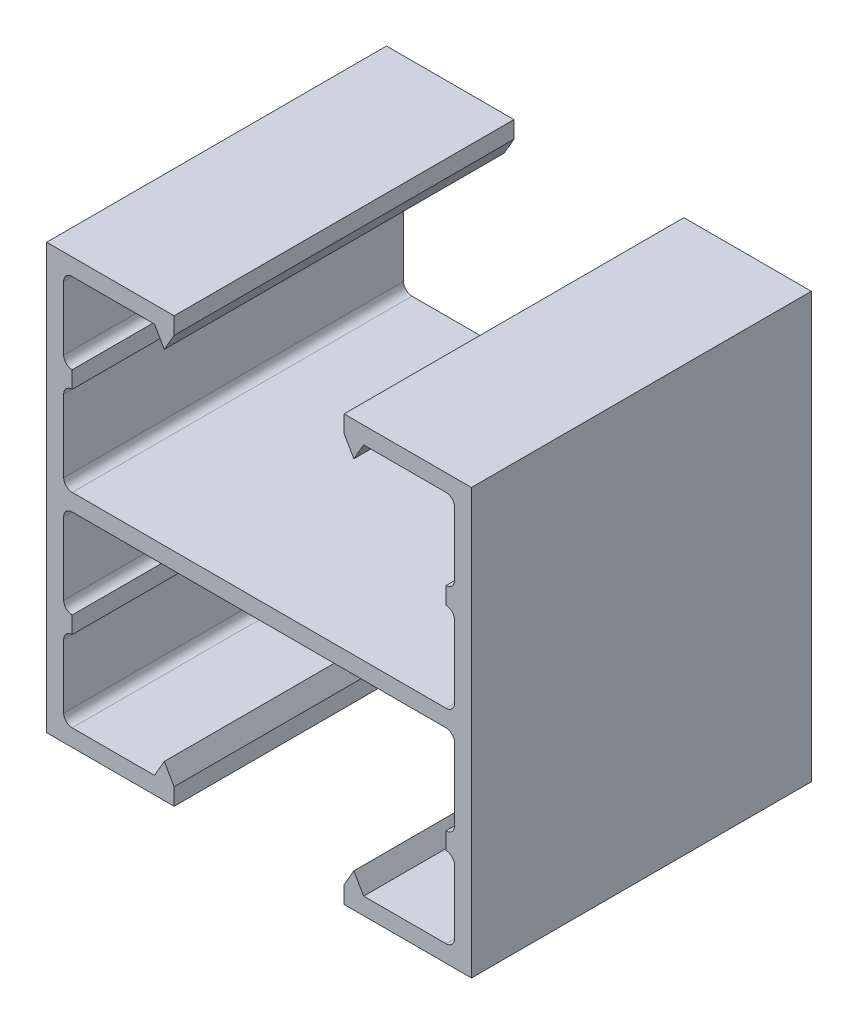
SolidWorks part; units mm, degrees
ref_plane "Plane1" through (0, 0, 0) normal (0, 0, 1) x (1, 0, 0)
ref_plane "Plane2" through (0, 0, 0) normal (0, 1, 0) x (1, 0, 0)
ref_plane "Plane3" through (0, 0, 0) normal (1, 0, 0) x (0, 0, -1)
sketch "Sketch1" plane through (0, 0, 0) normal (0, 0, 1) x (1, 0, 0)
  line L0 (-6.35, 15.875) -> (-15.875, 15.875)
  line L1 (-15.875, 15.875) -> (-15.875, -15.875)
  line L2 (-7.8165, -14.605) -> (-13.97, -14.605)
  line L3 (15.875, -15.875) -> (15.875, 15.875)
  line L4 (15.875, 15.875) -> (6.35, 15.875)
  line L5 (13.97, 14.605) -> (7.8165, 14.605)
  line L6 (14.605, 1.27) -> (14.605, 7.3025)
  line L7 (-13.97, 0.635) -> (13.97, 0.635)
  line L8 (-14.605, 13.97) -> (-14.605, 8.5725)
  line L9 (-7.8165, 14.605) -> (-13.97, 14.605)
  line L10 (7.8165, 14.605) -> (7.0832, 13.335)
  line L11 (7.0832, 13.335) -> (6.35, 14.605)
  line L12 (6.35, 14.605) -> (6.35, 15.875)
  line L13 (-7.8165, 14.605) -> (-7.0832, 13.335)
  line L14 (-7.0832, 13.335) -> (-6.35, 14.605)
  line L15 (-6.35, 14.605) -> (-6.35, 15.875)
  line L16 (22.86, 0) -> (-25.4, 0) construction
  line L17 (7.0832, -13.335) -> (6.35, -14.605)
  line L18 (7.8165, -14.605) -> (7.0832, -13.335)
  line L19 (13.97, -14.605) -> (7.8165, -14.605)
  line L20 (15.875, -15.875) -> (6.35, -15.875)
  line L21 (6.35, -14.605) -> (6.35, -15.875)
  line L22 (-6.35, -15.875) -> (-15.875, -15.875)
  line L23 (-6.35, -14.605) -> (-6.35, -15.875)
  line L24 (-7.0832, -13.335) -> (-6.35, -14.605)
  line L25 (-7.8165, -14.605) -> (-7.0832, -13.335)
  line L26 (-14.605, -13.97) -> (-14.605, -8.5725)
  line L27 (14.605, -1.27) -> (14.605, -7.3025)
  line L28 (-13.97, -0.635) -> (13.97, -0.635)
  line L29 (-14.605, 8.5725) -> (-13.97, 8.5725)
  line L30 (-13.97, 8.5725) -> (-13.97, 7.3025)
  line L31 (-13.97, 7.3025) -> (-14.605, 7.3025)
  line L32 (-14.605, 7.3025) -> (-14.605, 1.27)
  line L33 (14.605, 8.5725) -> (13.97, 8.5725)
  line L34 (13.97, 8.5725) -> (13.97, 7.3025)
  line L35 (13.97, 7.3025) -> (14.605, 7.3025)
  line L36 (14.605, 8.5725) -> (14.605, 13.97)
  line L37 (13.97, -7.3025) -> (14.605, -7.3025)
  line L38 (13.97, -8.5725) -> (13.97, -7.3025)
  line L39 (14.605, -8.5725) -> (13.97, -8.5725)
  line L40 (-13.97, -7.3025) -> (-14.605, -7.3025)
  line L41 (-13.97, -8.5725) -> (-13.97, -7.3025)
  line L42 (-14.605, -8.5725) -> (-13.97, -8.5725)
  line L43 (14.605, -8.5725) -> (14.605, -13.97)
  line L44 (-14.605, -7.3025) -> (-14.605, -1.27)
  arc A0 (-14.605, 1.27) -> (-13.97, 0.635) centre (-13.97, 1.27) ccw
  arc A1 (-13.97, 14.605) -> (-14.605, 13.97) centre (-13.97, 13.97) ccw
  arc A2 (14.605, 13.97) -> (13.97, 14.605) centre (13.97, 13.97) ccw
  arc A3 (13.97, 0.635) -> (14.605, 1.27) centre (13.97, 1.27) ccw
  arc A4 (14.605, -13.97) -> (13.97, -14.605) centre (13.97, -13.97) cw
  arc A5 (-13.97, -14.605) -> (-14.605, -13.97) centre (-13.97, -13.97) cw
  arc A6 (13.97, -0.635) -> (14.605, -1.27) centre (13.97, -1.27) cw
  arc A7 (-14.605, -1.27) -> (-13.97, -0.635) centre (-13.97, -1.27) cw
  dimension "D8" = 15.875
  dimension "D10" = 12.7
  dimension "D13" = 0.7332
  dimension "Height" = 31.75
  dimension "D3" = 15.875
  dimension "D1" = 0.635
  dimension "D6" = 8.5725
  dimension "D4" = 60
extrude "Base-Extrude" add sketch "Sketch1" along normal mid plane 25.4
fillet "Fillet1" radius 0.635 8 edges at (14.605, 8.5725, 0) (14.605, -7.3025, 0) (-14.605, 8.5725, 0) (-14.605, -7.3025, 0) (-14.605, 7.3025, 0) (-14.605, -8.5725, 0) (14.605, 7.3025, 0) (14.605, -8.5725, 0)
equation "\"D8@Sketch1\" = \"Width@Sketch1\" / 2"
equation "\"D10@Sketch1\" = \"Width@Sketch1\" - 2 * \"edge@Sketch1\""
equation "\"D5@Sketch1\" = \"gauge@Sketch1\" / 2"
equation "\"D3@Sketch1\" = \"Height@Sketch1\" / 2"
equation "\"D1@Sketch1\" = \"D5@Sketch1\""
equation "\"D6@Sketch1\" = \"D3@Sketch1\" / 2 + \"D5@Sketch1\""
equation "\"D1@Fillet1\" = \"D5@Sketch1\""
equation "\"D13@Sketch1\" = \"gauge@Sketch1\" * .577350269"
